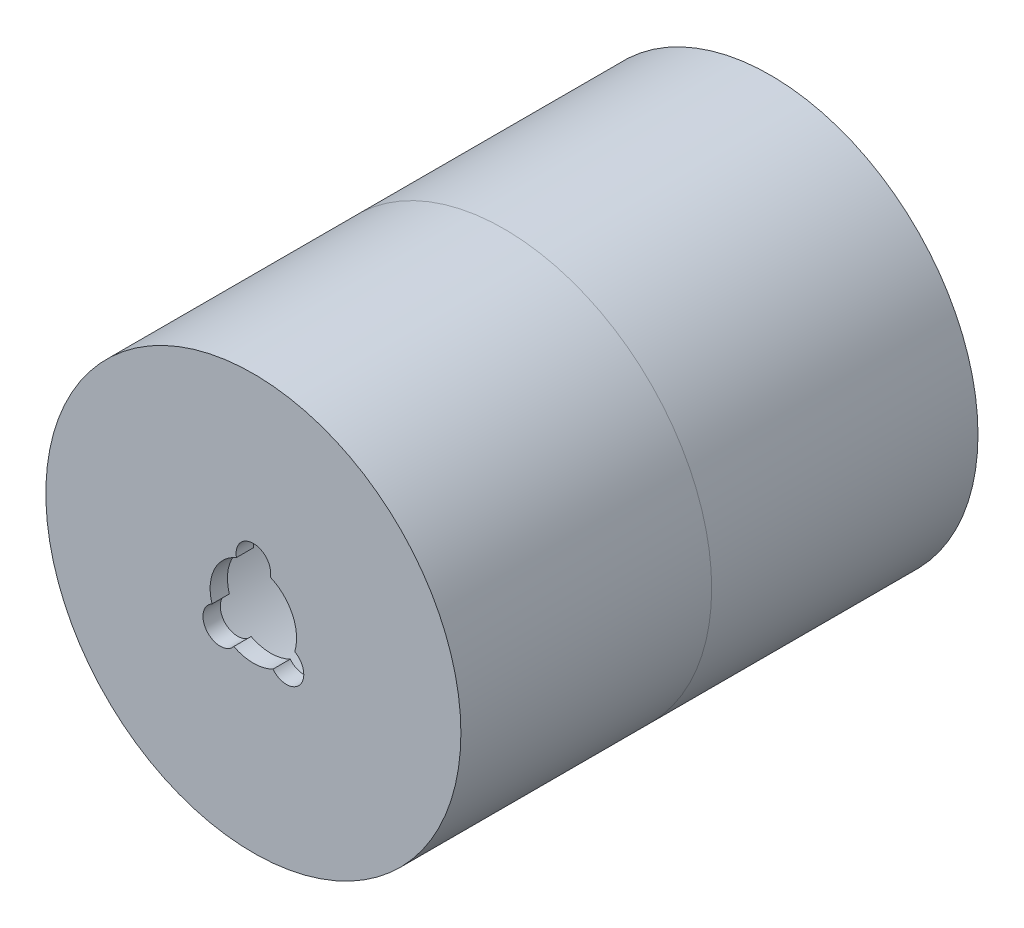
SolidWorks part; units mm, degrees
ref_plane "Front Plane" through (0, 0, 0) normal (0, 0, 1) x (1, 0, 0)
ref_plane "Top Plane" through (0, 0, 0) normal (0, 1, 0) x (1, 0, 0)
ref_plane "Right Plane" through (0, 0, 0) normal (1, 0, 0) x (0, 0, -1)
sketch "Sketch1" plane through (0, 0, 0) normal (1, 0, 0) x (0, 0, -1)
  line L0 (-59.8, 5) -> (-57.8, 5)
  line L1 (-59.8, 0) -> (0, 0)
  line L2 (-59.8, 0) -> (-59.8, 24)
  line L3 (-59.8, 24) -> (0, 24)
  line L4 (0, 0) -> (0, 24)
  line L5 (-1072.3815, 0) -> (1072.3815, 0) construction
  line L6 (-30.8, -974.342) -> (-30.8, 49025.6579)
  line L10 (-57.8, 0) -> (-1.8, 0)
  line L11 (-57.8, 0) -> (-57.8, 17)
  line L12 (-57.8, 17) -> (-1.8, 17)
  line L13 (-1.8, 0) -> (-1.8, 17)
  line L15 (-59.8, 18) -> (0, 18)
  line L16 (-27.3, 24) -> (-27.3, 18)
  line L17 (-1.8, 13) -> (0, 13)
  line L18 (-34.3, 24) -> (-34.3, 18)
  point P14 (-30.8, 17)
  dimension "D3" = 56
  dimension "D1" = 2
  dimension "D2" = 17
  dimension "D6" = 27
  dimension "D5" = 5
  dimension "D9" = 4
  dimension "D4" = 7
  dimension "D7" = 1.8
  dimension "D8" = 1
  dimension "D10" = 7
revolve "Revolve1" add sketch "Sketch1" angle 360 about L5 region at (0, 11.5, 59.4822) region at (0, 21, 47.05) region at (0, 21, 32.55) region at (0, 17.0263, 12.6526) region at (0, 21, 29.05) region at (0, 21, 13.65)
ref_axis "Axis1" through (0, 0, -68.4732) along (0, 0, 1)
ref_axis "Axis2" through (0, -974.342, 30.8) along (0, 1, 0)
ref_plane "Plane1" through (0, 0, 30.8) normal (0, 0, 1) x (1, 0, 0)
sketch "Sketch3" plane through (0, 0, 30.8) normal (0, 0, 1) x (1, 0, 0)
  line L0 (0, -999.5695) -> (0, 49000.4305) construction
  line L1 (-340.1578, -934.5758) -> (16760.8494, 46050.0552) construction
  line L2 (-1, 19.9722) -> (1, 19.9722)
  line L3 (338.8634, -931.0195) -> (-16762.1438, 46053.6116) construction
  line L4 (1, 19.9722) -> (4.5053, 16.5181) construction
  line L5 (0, 19.9722) -> (0, 23.1004) construction
  line L6 (2.0302, 19.9722) -> (-0.0328, 19.9722) construction
  line L7 (3.5103, 17.4986) -> (0.2863, 20.6756) construction
  line L8 (1, 19.9722) -> (1.1102, 22.1722) construction
  line L9 (4.5053, 16.5181) -> (4.684, 16.342)
  line L10 (6.5668, 18.0421) -> (7.5928, 20.8612)
  line L11 (-6.5668, 18.0421) -> (-7.5928, 20.8612)
  line L12 (-4.5053, 16.5181) -> (-4.684, 16.342)
  circle A4 centre (0, 0) radius 17 construction
  circle A6 centre (0, 0) radius 17
  circle A8 centre (5.2072, 17.2304) radius 1 construction
  arc A10 (6.5668, 18.0421) -> (-6.5668, 18.0421) centre (0, 0) cw
  circle A12 centre (0, 0) radius 23.2
  circle A13 centre (0, 0) radius 22.2
  circle A14 centre (0, 0) radius 67.8292
  spline S0 degree 3 poles (1, 19.9722) (1.8375, 19.9722) (3.4007, 17.6066) (4.5053, 16.5181) knots 0 0 0 0 1 1 1 1
  spline S1 degree 3 poles (-1, 19.9722) (-1.8375, 19.9722) (-3.4007, 17.6066) (-4.5053, 16.5181) knots 0 0 0 0 1 1 1 1
  point P11 (0, 19.9722)
  point P13 (5.8143, 15.9748)
  point P16 (0, 22.2)
  point P20 (0, 19.9722)
  dimension "D2" = 2
  dimension "D4" = 20
  dimension "D1" = 5.2
  dimension "D3" = 1
  dimension "D5" = 2.2
  dimension "D6" = 2.2
  dimension "D7" = 1
extrude "Cut-Extrude1" cut sketch "Sketch3" against normal mid plane 4 contours L10 A13 L11 A10 S1 L2 S0 L9 A6 L12 region at (0, -18.6353, 30.8)
extrude "Cut-Extrude2" cut sketch "Sketch3<5>" against normal mid plane 2 contours A6 | L2 S1 L12 A6 L9 S0 | L11 A13 L10 A10 region at (0, 18.1134, 30.8) region at (0, 0, 30.8) region at (7.661, 19.2401, 30.8)
sketch "Sketch3<5>" plane through (0, 0, 30.8) normal (0, 0, 1) x (1, 0, 0) same geometry as "Sketch3"
sketch "Sketch5" plane through (0, 0, 59.8) normal (0, 0, 1) x (1, 0, 0)
  line L0 (3.8302, -3.2139) -> (-3.8302, -3.2139) construction
  circle A3 centre (0, 5) radius 2
  circle A4 centre (-3.8302, -3.2139) radius 2
  circle A5 centre (3.8302, -3.2139) radius 2
  circle A6 centre (0, 0) radius 5
  circle A7 centre (0, 0) radius 5 construction
  point P7 (0, -3.2139)
  circle M6 centre (0, 0) radius 5
extrude "Cut-Extrude3" cut sketch "Sketch5" against normal up to next contours A6 A4 M6 | A3 M6 | A6 A5 M6 region at (0, 5.7727, 59.8) region at (-4.4222, -3.7106, 59.8) region at (4.4222, -3.7106, 59.8)
ref_plane "Plane6" through (0, 0, 30.8) normal (0, 0, 1) x (1, 0, 0)
split "Split4" trim tools "Plane6" bodies to split 112 resulting bodies 129 130
equation "\"key_pin_length\"= 25.00mm"
equation "\"key_pin_dia\"= 20.00mm"
equation "\"driver_pin_travel\"= 3.00mm"
equation "\"driver_pin_dia\"= 3mm"
equation "\"plug_wall_thickness\" = 2mm"
equation "\"plug_spring_solid_length\"= 2mm"
equation "\"plug_length\"= 2 * \"key_pin_length\" + 2 * \"plug_wall_thickness\" + \"plug_spring_solid_length\""
equation "\"D3@Sketch1\"= \"plug_length\""
equation "\"D6@Sketch1\"= \"plug_wall_thickness\" + \"key_pin_length\""
equation "\"D7@Sketch1\"=\"D1@Sketch1\"-\"allowance\""
equation "\"driver_pin_head_dia\" = 2mm"
equation "\"D1@Sketch3\"=\"driver_pin_head_dia\"+\"driver_pin_travel\"+\"allowance\""
equation "\"true_gate_depth\" = 1.25mm"
equation "\"D4@Sketch1\"=\"driver_pin_head_dia\" + \"driver_pin_travel\" + 2mm"
equation "\"driver_pin_neck_dia\"= 2.00mm"
equation "\"driver_pin_head_length\" = 2mm"
equation "\"D1@Cut-Extrude1\"= \"driver_pin_neck_dia\" + \"driver_pin_head_length\""
equation "\"D1@Cut-Extrude2\"=\"driver_pin_neck_dia\""
equation "\"plug_dia\"= \"key_pin_dia\" + 2*(\"driver_pin_travel\" + 1mm + \"plug_spring_solid_length\" + 1mm)"
equation "\"D2@Sketch1\"=\"plug_dia\"/2"
equation "\"D2@Sketch3\"=\"driver_pin_head_dia\""
equation "\"D5@Sketch3\"=\"driver_pin_head_dia\"+\"allowance\""
equation "\"D6@Sketch3\"=\"driver_pin_head_dia\"+\"allowance\""
equation "\"key_notches_dia\" = 4mm"
equation "\"key_notches_offset_angle\" = 25deg"
equation "\"key_offset_angle\" = 60deg"
equation "\"key_offset_len\" = 6mm"
equation "\"allowance\" = 0.2mm"
